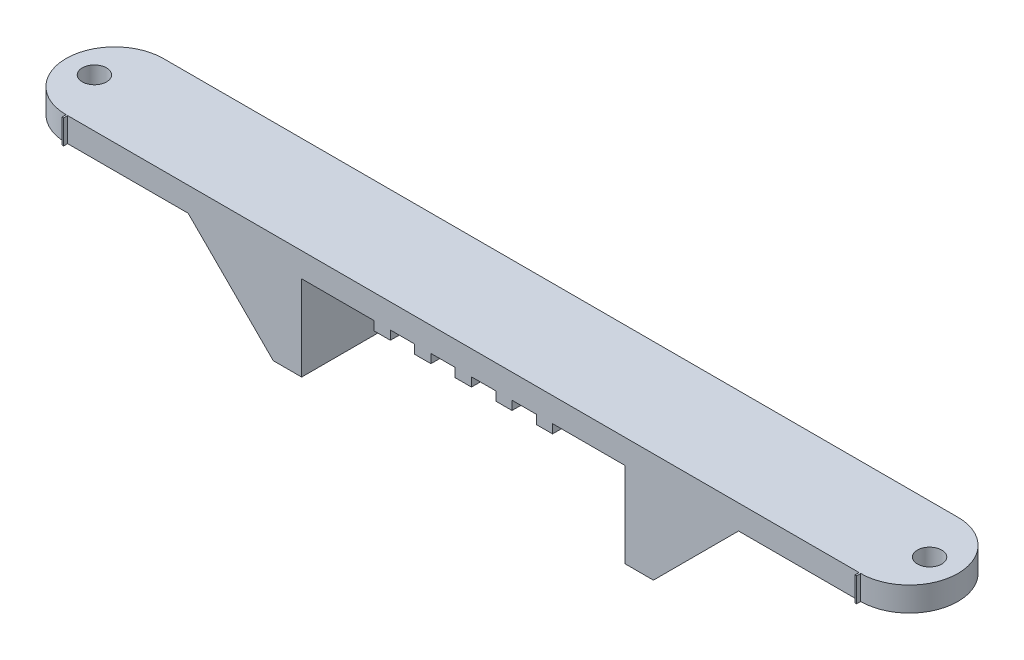
SolidWorks part; units mm, degrees
ref_plane "Front Plane" through (0, 0, 0) normal (0, 0, 1) x (1, 0, 0)
ref_plane "Top Plane" through (0, 0, 0) normal (0, 1, 0) x (1, 0, 0)
ref_plane "Right Plane" through (0, 0, 0) normal (1, 0, 0) x (0, 0, -1)
sketch "Sketch1" plane through (0, 0, 0) normal (0, 1, 0) x (1, 0, 0)
  line L0 (-49, 0) -> (49, 0) construction
  line L1 (-49, 6) -> (49, 6)
  line L2 (-49, -6) -> (49, -6)
  arc A0 (-49, 6) -> (-49, -6) centre (-49, 0) ccw
  arc A1 (49, -6) -> (49, 6) centre (49, 0) ccw
  circle A2 centre (-51.5, 0) radius 1.5
  circle A3 centre (51.5, 0) radius 1.5
  point P2 (0, 0)
  point P12 (-55, 0)
  point P13 (55, 0)
  dimension "D3" = 3
  dimension "D4" = 3.5
  dimension "D1" = 110
  dimension "D2" = 12
  dimension "D5" = 3.5
extrude "Boss-Extrude1" add sketch "Sketch1" along normal blind 3 contours L2 A1 L1 A0 | A2 | A3
sketch "Sketch4" plane through (0, 0, 0) normal (0, -1, 0) x (1, 0, 0)
  line L0 (-19.94, 6) -> (-19.94, -6)
  line L1 (-49, 6) -> (49, 6) construction
  line L2 (-49, -6) -> (49, -6) construction
  line L3 (-19.94, -6) -> (-23.44, -6)
  line L4 (-23.44, -6) -> (-23.44, 6)
  line L5 (-23.44, 6) -> (-19.94, 6)
  line L6 (0, 6) -> (0, -6) construction
  line L7 (-19.94, 5.075) -> (-19.94, -14.3256) construction
  line L8 (23.44, -6) -> (23.44, 6)
  line L9 (19.94, -6) -> (23.44, -6)
  line L10 (19.94, 6) -> (19.94, -6)
  line L11 (23.44, 6) -> (19.94, 6)
  dimension "D1" = 0
  dimension "D2" = 3.5
extrude "Boss-Extrude3" add sketch "Sketch4" along normal blind 10.5
sketch "Sketch5" plane through (0, 0, 0) normal (0, -1, 0) x (1, 0, 0)
  line L1 (4, 6) -> (4, -6)
  line L2 (4, 6) -> (6, 6)
  line L6 (-19.94, -6) -> (19.94, -6) construction
  line L7 (-1, 6) -> (1, 6)
  line L8 (-1, 6) -> (-1, -6)
  line L9 (-1, -6) -> (1, -6)
  line L10 (1, 6) -> (1, -6)
  line L11 (-1, 6) -> (1, -6) construction
  line L12 (-1, -6) -> (1, 6) construction
  line L13 (6, 6) -> (6, -6)
  line L14 (4, -6) -> (6, -6)
  line L15 (9, 6) -> (9, -6)
  line L16 (9, 6) -> (11, 6)
  line L17 (11, 6) -> (11, -6)
  line L18 (9, -6) -> (11, -6)
  line L19 (-4, 6) -> (-4, -6)
  line L20 (-6, -6) -> (-4, -6)
  line L21 (-6, 6) -> (-6, -6)
  line L22 (-6, 6) -> (-4, 6)
  line L23 (-9, 6) -> (-9, -6)
  line L24 (-11, -6) -> (-9, -6)
  line L25 (-11, 6) -> (-11, -6)
  line L26 (-11, 6) -> (-9, 6)
  point P0 (0, 0)
  dimension "D1" = 2
  dimension "D2" = 3
  dimension "D3" = 3
extrude "Boss-Extrude4" add sketch "Sketch5" along normal blind 1.1
sketch "Sketch6" plane through (0, 0, 6) normal (0, 0, 1) x (1, 0, 0)
  line L0 (49, 0) -> (49, 3)
  line L1 (49, 3) -> (48.8, 3)
  line L2 (-49, 3) -> (49, 3) construction
  line L3 (48.8, 3) -> (48.8, 0)
  line L4 (23.44, 0) -> (49, 0) construction
  line L5 (48.8, 0) -> (49, 0)
  line L6 (0, 0) -> (0, 3) construction
  line L7 (-48.8, 0) -> (-49, 0)
  line L8 (-48.8, 3) -> (-48.8, 0)
  line L9 (-49, 3) -> (-48.8, 3)
  line L10 (-49, 0) -> (-49, 3)
  dimension "D1" = 0.2
extrude "Boss-Extrude5" add sketch "Sketch6" along normal blind 0.5 contours L0 L1 L3 L5 | L8 L7 L10 L9
chamfer "Chamfer1" distance 10.5 2 edges at (23.44, 0, 0) (-23.44, 0, 0)
